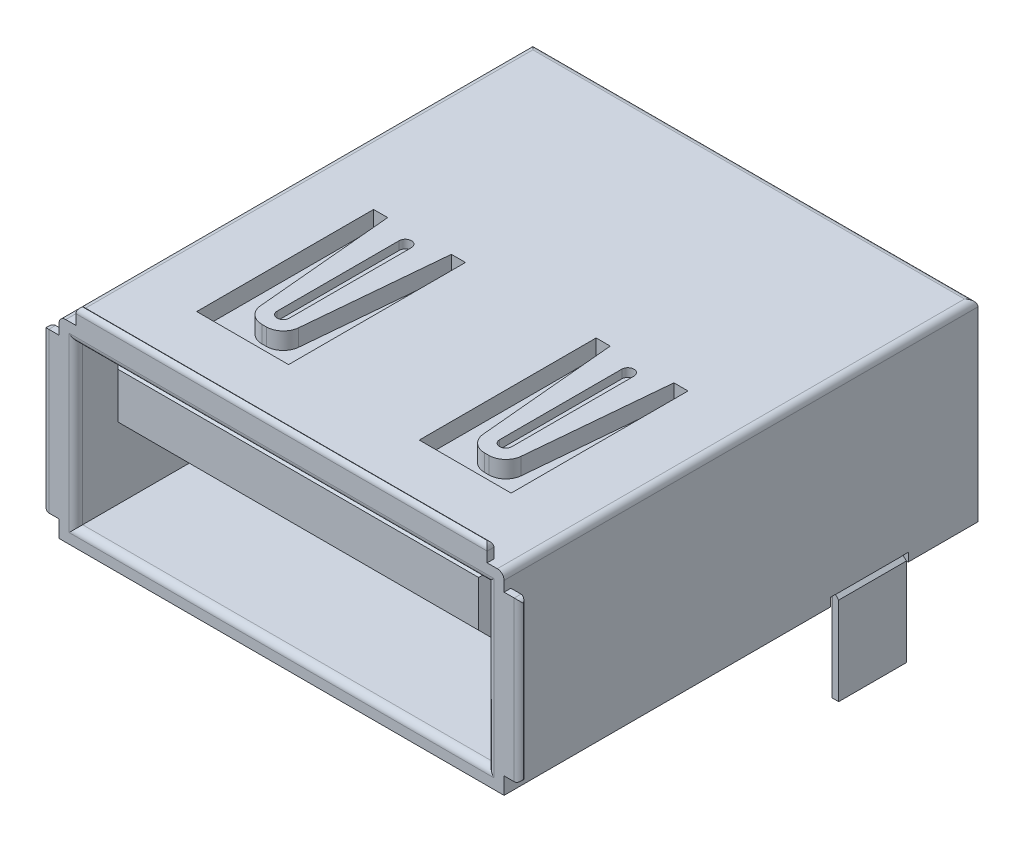
SolidWorks part; units mm, degrees
ref_plane "前视基准面" through (0, 0, 0) normal (0, 0, 1) x (1, 0, 0)
ref_plane "上视基准面" through (0, 0, 0) normal (0, 1, 0) x (1, 0, 0)
ref_plane "右视基准面" through (0, 0, 0) normal (1, 0, 0) x (0, 0, -1)
sketch "草图1" plane through (0, 0, 0) normal (0, 0, 1) x (1, 0, 0)
  line L1 (-6.575, -2.85) -> (6.575, -2.85)
  line L2 (-6.575, -2.85) -> (-6.575, 2.85)
  line L3 (-6.575, 2.85) -> (6.575, 2.85)
  line L4 (6.575, -2.85) -> (6.575, 2.85)
  line L5 (-6.575, -2.85) -> (6.575, 2.85) construction
  line L6 (-6.575, 2.85) -> (6.575, -2.85) construction
  line L7 (-6.075, -2.35) -> (6.075, -2.35)
  line L8 (-6.075, -2.35) -> (-6.075, 2.35)
  line L9 (-6.075, 2.35) -> (6.075, 2.35)
  line L10 (6.075, -2.35) -> (6.075, 2.35)
  line L11 (-6.075, -2.35) -> (6.075, 2.35) construction
  line L12 (-6.075, 2.35) -> (6.075, -2.35) construction
  point P0 (0, 0)
  point P6 (0, 0)
  dimension "D1" = 13.15
  dimension "D2" = 5.7
  dimension "D3" = 0.5
  dimension "D4" = 0.5
extrude "凸台-拉伸1" add sketch "草图1" along normal blind 14
sketch "草图2" plane through (0, 0, 0) normal (0, 0, 1) x (1, 0, 0)
  line L1 (6.575, -2.85) -> (-6.575, -2.85)
  line L2 (6.575, -2.85) -> (6.575, 2.85)
  line L3 (6.575, 2.85) -> (-6.575, 2.85)
  line L4 (-6.575, -2.85) -> (-6.575, 2.85)
  line L5 (6.575, -2.85) -> (-6.575, 2.85) construction
  line L6 (6.575, 2.85) -> (-6.575, -2.85) construction
  point P0 (0, 0)
extrude "凸台-拉伸2" add sketch "草图2" along normal blind 0.5
sketch "草图3" plane through (0, 0, 0.5) normal (0, 0, 1) x (1, 0, 0)
  line L0 (-6.075, 2.35) -> (-6.075, -2.35) construction
  line L1 (5.575, 0.25) -> (-5.575, 0.25)
  line L2 (5.575, 0.25) -> (5.575, 2.1)
  line L3 (5.575, 2.1) -> (-5.575, 2.1)
  line L4 (-5.575, 0.25) -> (-5.575, 2.1)
  line L5 (5.575, 0.25) -> (-5.575, 2.1) construction
  line L6 (5.575, 2.1) -> (-5.575, 0.25) construction
  line L7 (6.075, 2.35) -> (-6.075, 2.35) construction
  point P0 (0, 1.175)
  point P1 (0, 1.175)
  point P7 (0, 0)
  point P10 (0, 0)
  dimension "D1" = 0.25
  dimension "D2" = 0.5
  dimension "D3" = 0.25
extrude "凸台-拉伸3" add sketch "草图3" along normal blind 13 separate body
chamfer "倒角1" distance 0.25 angle 45 4 edges at (5.575, 1.175, 13.5) (0, 0.25, 13.5) (-5.575, 1.175, 13.5) (0, 2.1, 13.5)
sketch "草图4" plane through (0, -2.85, 0) normal (0, -1, 0) x (1, 0, 0)
  line L0 (-1, 0.5) -> (1, 0.5) construction
  line L1 (3.5, 0.5) -> (-3.5, 0.5) construction
  line L2 (0, 0.5) -> (0, 3.21) construction
  line L3 (-6.57, 3.21) -> (6.57, 3.21) construction
  line L4 (-6.575, 0) -> (6.575, 0) construction
  circle A0 centre (-1, 0.5) radius 0.46
  circle A1 centre (1, 0.5) radius 0.46
  circle A2 centre (-3.5, 0.5) radius 0.46
  circle A3 centre (3.5, 0.5) radius 0.46
  circle A4 centre (-6.57, 3.21) radius 1.15
  circle A5 centre (6.57, 3.21) radius 1.15
  point P3 (0, 0.5)
  point P9 (0, 0.5)
  point P15 (0, 3.21)
  dimension "D2" = 0.92
  dimension "D3" = 0.92
  dimension "D4" = 0.92
  dimension "D5" = 0.92
  dimension "D10" = 2.3
  dimension "D11" = 2.3
  dimension "D1" = 2
  dimension "D6" = 2.5
  dimension "D7" = 2.5
  dimension "D8" = 2.71
  dimension "D9" = 13.14
  dimension "D12" = 0.5
extrude "切除-拉伸2" cut sketch "草图4" against normal blind 0.25
sketch "草图7" plane through (0, -2.6, -2.85) normal (0, 1, 0) x (-1, 0, 0)
  line L0 (-1, 3.35) -> (1, 3.35) construction
  line L1 (3.5, 3.35) -> (-3.5, 3.35) construction
  line L2 (0, 3.35) -> (0, 6.06) construction
  line L3 (-6.57, 6.06) -> (6.57, 6.06) construction
  line L4 (-3.125, 3.25) -> (-3.125, 3.45)
  line L5 (-0.65, 3.25) -> (-0.65, 3.45)
  line L6 (3.875, 3.25) -> (3.125, 3.25)
  line L7 (3.875, 3.25) -> (3.875, 3.45)
  line L8 (3.875, 3.45) -> (3.125, 3.45)
  line L9 (3.125, 3.25) -> (3.125, 3.45)
  line L10 (3.875, 3.25) -> (3.125, 3.45) construction
  line L11 (3.875, 3.45) -> (3.125, 3.25) construction
  line L12 (-3.125, 3.25) -> (-3.875, 3.25)
  line L13 (-3.875, 3.25) -> (-3.875, 3.45)
  line L14 (-3.125, 3.45) -> (-3.875, 3.45)
  line L15 (-0.65, 3.25) -> (-1.35, 3.25)
  line L16 (1.35, 3.25) -> (0.65, 3.25)
  line L17 (1.35, 3.25) -> (1.35, 3.45)
  line L18 (1.35, 3.45) -> (0.65, 3.45)
  line L19 (0.65, 3.25) -> (0.65, 3.45)
  line L20 (1.35, 3.25) -> (0.65, 3.45) construction
  line L21 (1.35, 3.45) -> (0.65, 3.25) construction
  line L22 (-1.35, 3.25) -> (-1.35, 3.45)
  line L23 (-0.65, 3.45) -> (-1.35, 3.45)
  line L25 (6.47, 5.06) -> (6.67, 5.06)
  line L26 (6.47, 5.06) -> (6.47, 7.06)
  line L27 (6.47, 7.06) -> (6.67, 7.06)
  line L28 (6.67, 5.06) -> (6.67, 7.06)
  line L29 (6.47, 5.06) -> (6.67, 7.06) construction
  line L30 (6.47, 7.06) -> (6.67, 5.06) construction
  line L31 (-6.47, 5.06) -> (-6.67, 5.06)
  line L32 (-6.47, 5.06) -> (-6.47, 7.06)
  line L33 (-6.47, 7.06) -> (-6.67, 7.06)
  line L34 (-6.67, 5.06) -> (-6.67, 7.06)
  line L35 (-6.47, 5.06) -> (-6.67, 7.06) construction
  line L36 (-6.47, 7.06) -> (-6.67, 5.06) construction
  circle A0 centre (-1, 3.35) radius 0.46 construction
  circle A1 centre (1, 3.35) radius 0.46 construction
  circle A2 centre (-3.5, 3.35) radius 0.46 construction
  circle A3 centre (3.5, 3.35) radius 0.46 construction
  circle A4 centre (-6.57, 6.06) radius 1.15 construction
  circle A5 centre (6.57, 6.06) radius 1.15 construction
  point P3 (0, 3.35)
  point P9 (0, 3.35)
  point P15 (0, 6.06)
  dimension "D2" = 0.92
  dimension "D3" = 0.92
  dimension "D4" = 0.92
  dimension "D5" = 0.92
  dimension "D10" = 2.3
  dimension "D11" = 2.3
  dimension "D1" = 2
  dimension "D6" = 2.5
  dimension "D7" = 2.5
  dimension "D8" = 2.71
  dimension "D9" = 13.14
  dimension "D12" = 0.5
  dimension "D13" = 0.75
  dimension "D14" = 0.2
  dimension "D16" = 0.7
  dimension "D17" = 0.2
  dimension "D19" = 0.2
  dimension "D20" = 2
  dimension "D21" = 0.2
  dimension "D22" = 2
  dimension "D15" = 2
  dimension "D18" = 2
extrude "凸台-拉伸4" add sketch "草图7" against normal blind 2.8
chamfer "倒角3" distance 0.1 angle 45 2 edges at (6.67, -2.6, 3.21) (-6.67, -2.6, 3.21)
chamfer "倒角4" distance 0.1 angle 45 24 edges at (-6.57, -5.4, 4.21) (-6.47, -5.4, 3.21) (-6.57, -5.4, 2.21) (-6.67, -5.4, 3.21) (-3.5, -5.4, 0.4) (-3.875, -5.4, 0.5) (-3.5, -5.4, 0.6) (-3.125, -5.4, 0.5) (-1, -5.4, 0.4) (-1.35, -5.4, 0.5) (-1, -5.4, 0.6) (-0.65, -5.4, 0.5) (1.35, -5.4, 0.5) (1, -5.4, 0.4) (0.65, -5.4, 0.5) (1, -5.4, 0.6) (3.875, -5.4, 0.5) (3.5, -5.4, 0.4) (3.125, -5.4, 0.5) (3.5, -5.4, 0.6) (6.57, -5.4, 2.21) (6.47, -5.4, 3.21) (6.57, -5.4, 4.21) (6.67, -5.4, 3.21)
sketch "草图8" plane through (0, 2.85, 0) normal (0, 1, 0) x (1, 0, 0)
  line L0 (0, -14) -> (0, 0) construction
  line L1 (6.575, -14) -> (-6.575, -14) construction
  line L2 (0, -9.2488) -> (-6.575, -9.2488) construction
  line L3 (-6.575, -14) -> (-6.575, 0) construction
  line L8 (-3.8088, -11.225) -> (-2.7662, -11.225)
  line L9 (-1.9305, -11.8618) -> (-4.6445, -11.8618)
  line L10 (-1.9305, -11.8618) -> (-1.9305, -6.6359)
  line L11 (-1.9305, -6.6359) -> (-2.3469, -6.6359)
  line L12 (-4.6445, -11.8618) -> (-4.6445, -6.6359)
  line L13 (-1.9305, -11.8618) -> (-4.6445, -6.6359) construction
  line L14 (-1.9305, -6.6359) -> (-4.6445, -11.8618) construction
  line L15 (-3.8088, -11.225) -> (-4.2281, -6.6359)
  line L16 (-3.2875, -9.2488) -> (-3.2875, -8.2037) construction
  line L17 (-2.7662, -11.225) -> (-2.3469, -6.6359)
  line L18 (-4.2281, -6.6359) -> (-4.6445, -6.6359)
  line L19 (3.8088, -11.225) -> (4.2281, -6.6359)
  line L20 (3.8088, -11.225) -> (2.7662, -11.225)
  line L21 (2.7662, -11.225) -> (2.3469, -6.6359)
  line L22 (1.9305, -6.6359) -> (2.3469, -6.6359)
  line L23 (1.9305, -11.8618) -> (1.9305, -6.6359)
  line L24 (1.9305, -11.8618) -> (4.6445, -11.8618)
  line L25 (4.6445, -11.8618) -> (4.6445, -6.6359)
  line L26 (4.2281, -6.6359) -> (4.6445, -6.6359)
  point P5 (-3.2875, -9.2488)
  point P8 (0, -9.2488)
  point P14 (-3.2875, -9.2488)
  point P19 (-3.2875, -11.225)
  point P31 (0, -9.2488)
extrude "切除-拉伸3" cut sketch "草图8" against normal blind 0.5
sketch "草图9" plane through (0, 2.85, 0) normal (0, 1, 0) x (1, 0, 0)
  line L0 (-3.2875, -10.663) -> (-3.2875, -7.0562) construction
  line L1 (-3.4673, -10.663) -> (-3.4673, -7.0562)
  line L2 (-3.1077, -10.663) -> (-3.1077, -7.0562)
  line L3 (0, 0) -> (0, -14) construction
  line L4 (6.575, 0) -> (-6.575, 0) construction
  line L5 (6.575, -14) -> (-6.575, -14) construction
  line L6 (3.2875, -10.663) -> (3.2875, -7.0562) construction
  line L7 (3.4673, -10.663) -> (3.4673, -7.0562)
  line L8 (3.1077, -10.663) -> (3.1077, -7.0562)
  arc A0 (-3.4673, -10.663) -> (-3.1077, -10.663) centre (-3.2875, -10.663) ccw
  arc A1 (-3.1077, -7.0562) -> (-3.4673, -7.0562) centre (-3.2875, -7.0562) ccw
  arc A2 (3.4673, -10.663) -> (3.1077, -10.663) centre (3.2875, -10.663) cw
  arc A3 (3.1077, -7.0562) -> (3.4673, -7.0562) centre (3.2875, -7.0562) cw
  point P2 (-3.2875, -8.8596)
  point P15 (3.2875, -8.8596)
extrude "切除-拉伸4" cut sketch "草图9" against normal blind 0.25
fillet "圆角1" radius 0.5 4 edges at (3.8088, 2.6, 11.225) (2.7662, 2.6, 11.225) (-3.8088, 2.6, 11.225) (-2.7662, 2.6, 11.225)
sketch "草图11" plane through (-6.575, 0, 0) normal (-1, 0, 0) x (0, 0, 1)
  line L0 (14, 2.85) -> (14, -2.85) construction
  line L5 (14, 2.35) -> (13.8, 2.35)
  line L6 (14, 2.35) -> (14, -2.35)
  line L7 (14, -2.35) -> (13.8, -2.35)
  line L8 (13.8, 2.35) -> (13.8, -2.35)
  dimension "D1" = 0.5
  dimension "D2" = 0.5
  dimension "D3" = 0.2
extrude "凸台-拉伸5" add sketch "草图11" along normal blind 0.5
fillet "圆角2" radius 0.2 4 edges at (-7.075, -2.35, 13.9) (-7.075, 0, 13.8) (-7.075, 2.35, 13.9) (-7.075, 0, 14)
mirror "镜向1" about plane through (0, 0, 0) normal (1, 0, 0) of "圆角2", "凸台-拉伸5"
sketch "草图12" plane through (0, 2.85, 0) normal (0, 1, 0) x (1, 0, 0)
  line L0 (6.575, -14) -> (-6.575, -14) construction
  line L1 (-6.075, -14) -> (6.075, -14)
  line L2 (-6.075, -14) -> (-6.075, -13.8)
  line L3 (-6.075, -13.8) -> (6.075, -13.8)
  line L4 (6.075, -14) -> (6.075, -13.8)
  dimension "D1" = 0.5
  dimension "D2" = 0.5
  dimension "D3" = 0.2
extrude "凸台-拉伸6" add sketch "草图12" along normal blind 0.5
fillet "圆角3" radius 0.2 4 edges at (0, 3.35, 13.8) (6.075, 3.35, 13.9) (0, 3.35, 14) (-6.075, 3.35, 13.9)
fillet "圆角4" radius 0.2 4 edges at (0, -2.35, 14) (6.075, 0, 14) (0, 2.35, 14) (-6.075, 0, 14)
fillet "圆角5" radius 0.2 3 edges at (0, 2.85, 0) (6.575, 2.85, 7) (-6.575, 2.85, 7)
